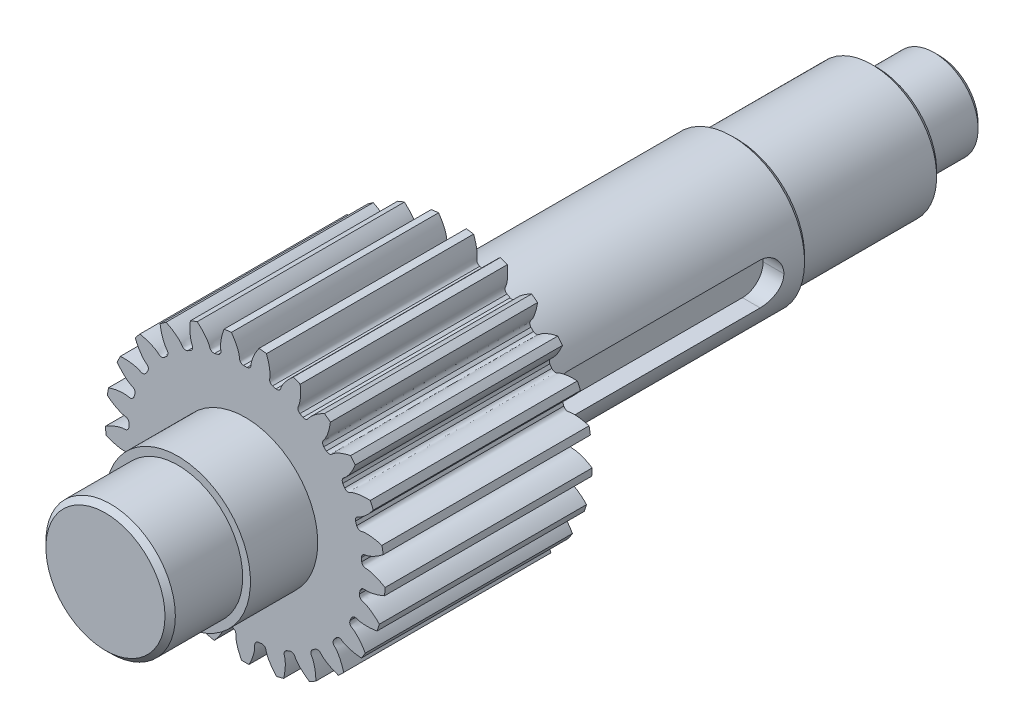
SolidWorks part; units mm, degrees
ref_plane "前视基准面" through (0, 0, 0) normal (0, 0, 1) x (1, 0, 0)
ref_plane "上视基准面" through (0, 0, 0) normal (0, 1, 0) x (1, 0, 0)
ref_plane "右视基准面" through (0, 0, 0) normal (1, 0, 0) x (0, 0, -1)
sketch "草图1" plane through (0, 0, 0) normal (0, 0, 1) x (1, 0, 0)
  circle A0 centre (0, 0) radius 27
extrude "凸台-拉伸1" add sketch "草图1" along normal blind 40
ref_axis "基准轴1" through (0, 0, 40) along (0, 0, -1)
sketch "草图2" plane through (0, 0, 0) normal (0, 0, 1) x (1, 0, 0)
  line L0 (0, 0) -> (0, 27) construction
  circle A0 centre (0, 0) radius 27 construction
  arc A1 (0.3441, 22.4974) -> (-0.3441, 22.4974) centre (0, 0) ccw
  arc A2 (6.4105, 30.6297) -> (-6.4105, 30.6297) centre (0, 0) ccw
  spline S0 degree 3 poles (0.3441, 22.4974) (1.1467, 22.6702) (1.071, 23.1545) (1.1484, 23.6361) (1.1592, 23.6962) (1.1732, 23.7653) (1.1905, 23.8433) (1.2116, 23.93) (1.2368, 24.0254) (1.2665, 24.1293) (1.301, 24.2416) (1.3407, 24.3621) (1.3859, 24.4906) (1.437, 24.6271) (1.4943, 24.7712) (1.5581, 24.9227) (1.6287, 25.0816) (1.7064, 25.2475) (1.7916, 25.4203) (1.8846, 25.5997) (1.9857, 25.7854) (2.095, 25.9773) (2.2131, 26.175) (2.34, 26.3782) (2.4761, 26.5868) (2.6216, 26.8004) (2.7768, 27.0186) (2.9419, 27.2413) (3.1172, 27.468) (3.303, 27.6986) (3.4993, 27.9325) (3.7064, 28.1696) (3.9246, 28.4094) (4.1539, 28.6517) (4.3947, 28.896) (4.647, 29.142) (4.9111, 29.3893) (5.187, 29.6376) (5.475, 29.8865) (5.8799, 30.2225) (6.1949, 30.4682) (6.4105, 30.6297) knots 0 0 0 0 0.130741 0.135745 0.141658 0.148481 0.156214 0.164857 0.174409 0.184871 0.196243 0.208524 0.221715 0.235816 0.250827 0.266748 0.283578 0.301318 0.319968 0.339527 0.359996 0.381375 0.403664 0.426862 0.450971 0.475988 0.501916 0.528753 0.556501 0.585157 0.614724 0.6452 0.676587 0.708882 0.742088 0.776203 0.811228 0.847163 0.884008 0.921762 1 1 1 1
  spline S1 degree 3 poles (-0.3441, 22.4974) (-1.1467, 22.6702) (-1.071, 23.1545) (-1.1484, 23.6361) (-1.1592, 23.6962) (-1.1732, 23.7653) (-1.1905, 23.8433) (-1.2116, 23.93) (-1.2368, 24.0254) (-1.2665, 24.1293) (-1.301, 24.2416) (-1.3407, 24.3621) (-1.3859, 24.4906) (-1.437, 24.6271) (-1.4943, 24.7712) (-1.5581, 24.9227) (-1.6287, 25.0816) (-1.7064, 25.2475) (-1.7916, 25.4203) (-1.8846, 25.5997) (-1.9857, 25.7854) (-2.095, 25.9773) (-2.2131, 26.175) (-2.34, 26.3782) (-2.4761, 26.5868) (-2.6216, 26.8004) (-2.7768, 27.0186) (-2.9419, 27.2413) (-3.1172, 27.468) (-3.303, 27.6986) (-3.4993, 27.9325) (-3.7064, 28.1696) (-3.9246, 28.4094) (-4.1539, 28.6517) (-4.3947, 28.896) (-4.647, 29.142) (-4.9111, 29.3893) (-5.187, 29.6376) (-5.475, 29.8865) (-5.8799, 30.2225) (-6.1949, 30.4682) (-6.4105, 30.6297) knots 0 0 0 0 0.130741 0.135745 0.141658 0.148481 0.156214 0.164857 0.174409 0.184871 0.196243 0.208524 0.221715 0.235816 0.250827 0.266748 0.283578 0.301318 0.319968 0.339527 0.359996 0.381375 0.403664 0.426862 0.450971 0.475988 0.501916 0.528753 0.556501 0.585157 0.614724 0.6452 0.676587 0.708882 0.742088 0.776203 0.811228 0.847163 0.884008 0.921762 1 1 1 1
extrude "切除-拉伸1" cut sketch "草图2" along normal through all
pattern_circular "阵列(圆周)1" count 25 every 14.4 about axis through (0, 0, 40) along (0, 0, -1) of "切除-拉伸1"
sketch "草图3" plane through (0, 0, 0) normal (0, 0, 1) x (1, 0, 0)
  circle A0 centre (0, 0) radius 25 construction
  dimension "Dn" = 50
sketch "草图4" plane through (0, 0, 40) normal (0, 0, 1) x (1, 0, 0)
  circle A0 centre (0, 0) radius 14
  dimension "D1" = 28
extrude "凸台-拉伸2" add sketch "草图4" along normal blind 13
sketch "草图5" plane through (0, 0, 53) normal (0, 0, 1) x (1, 0, 0)
  circle A0 centre (0, 0) radius 12.5
  dimension "D1" = 25
extrude "凸台-拉伸3" add sketch "草图5" along normal blind 14
chamfer "倒角2" distance 1 angle 45 1 edges at (12.5, 0, 67)
sketch "草图6" plane through (0, 0, 0) normal (0, 0, -1) x (-1, 0, 0)
  circle A0 centre (0, 0) radius 14
  dimension "D1" = 28
extrude "凸台-拉伸4" add sketch "草图6" along normal blind 55
sketch "草图7" plane through (0, 0, -55) normal (0, 0, -1) x (-1, 0, 0)
  circle A0 centre (0, 0) radius 12.5
  dimension "D1" = 25
extrude "凸台-拉伸5" add sketch "草图7" along normal blind 27
cosmetic thread "装饰螺纹线2" parameters "D2"=5
sketch "草图8" plane through (0, 0, -82) normal (0, 0, -1) x (-1, 0, 0)
  circle A0 centre (0, 0) radius 8.5
  dimension "D1" = 17
extrude "凸台-拉伸6" add sketch "草图8" along normal blind 12
sketch "草图9" plane through (0, 0, 0) normal (0, 1, 0) x (1, 0, 0)
  line L0 (14, 0) -> (14, 55) construction
  line L1 (14, 50) -> (10, 50)
  line L2 (14, 50) -> (14, 5)
  line L3 (14, 5) -> (10, 5)
  line L4 (10, 50) -> (10, 5)
  line L5 (24.1157, 0) -> (19.1795, 0) construction
  dimension "D1" = 45
  dimension "D2" = 5
  dimension "D3" = 4
extrude "切除-拉伸2" cut sketch "草图9" against normal blind 4 and the other way blind 4
fillet "圆角1" radius 4 4 edges at (11.7082, 4, -50) (11.7082, -4, -50) (11.7082, 4, -5) (11.7082, -4, -5)
chamfer "倒角3" distance 1 angle 45 3 edges at (-8.5, 0, -94) (-12.5, 0, -82) (-14, 0, -55)
